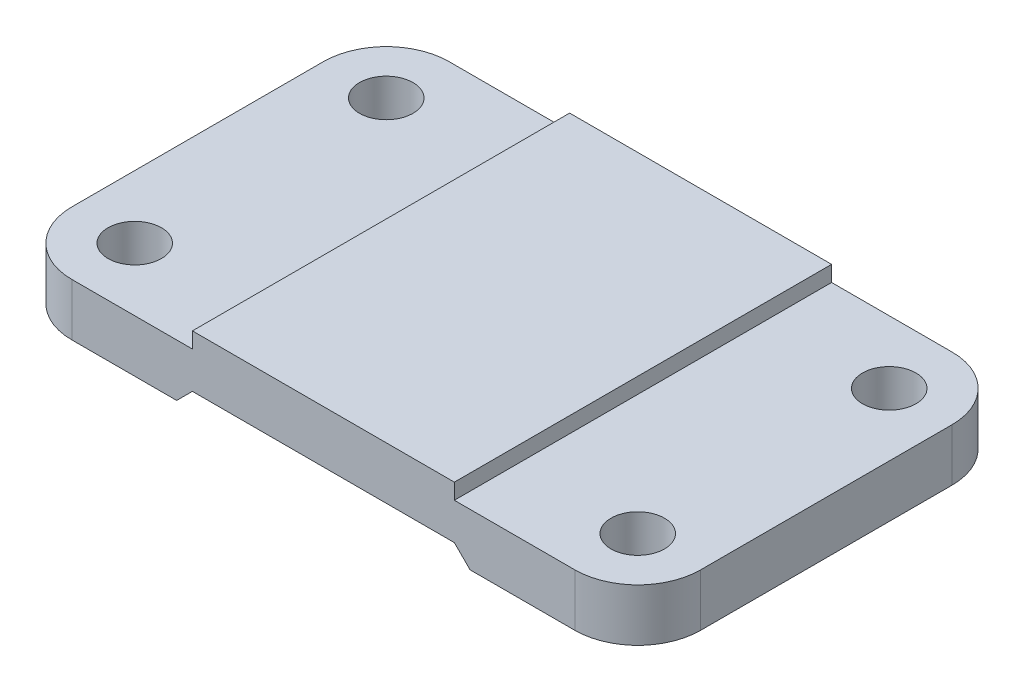
SolidWorks part; units mm, degrees
ref_plane "Front Plane" through (0, 0, 0) normal (0, 0, 1) x (1, 0, 0)
ref_plane "Top Plane" through (0, 0, 0) normal (0, 1, 0) x (1, 0, 0)
ref_plane "Right Plane" through (0, 0, 0) normal (1, 0, 0) x (0, 0, -1)
sketch "Sketch1" plane through (0, 0, 0) normal (0, 1, 0) x (1, 0, 0)
  line L1 (-60, -36) -> (60, -36)
  line L2 (-60, -36) -> (-60, 36)
  line L3 (-60, 36) -> (60, 36)
  line L4 (60, -36) -> (60, 36)
  line L5 (-60, -36) -> (60, 36) construction
  line L6 (-60, 36) -> (60, -36) construction
  point P0 (0, 0)
  dimension "D1" = 120
  dimension "D2" = 72
extrude "Boss-Extrude1" add sketch "Sketch1" along normal blind 10
fillet "Fillet1" radius 12 4 edges at (-60, 5, -36) (60, 5, -36) (60, 5, 36) (-60, 5, 36)
hole_wizard "M12 Tapped Hole1" positions "Sketch2" profile "Sketch3" tap size "M12" standard "DIN" end condition up to next
sketch "Sketch2" plane through (0, 0, 0) normal (0, 1, 0) x (1, 0, 0)
  point P6 (-48, 24)
  point P9 (48, 24)
  point P12 (48, -24)
  point P15 (-48, -24)
sketch "Sketch3" plane through (-48, 0, -24) normal (1, 0, 0) x (0, 0, -1)
  line L0 (0, 0) -> (0, 10)
  line L1 (0, 10) -> (5.1, 10)
  line L2 (5.1, 10) -> (5.1, 0.925)
  line L3 (5.1, 0.925) -> (6.025, 0)
  line L5 (6.025, 0) -> (0, 0)
  line L6 (-5.1, 0.925) -> (-6.025, 0) construction
  line L11 (0, -6.35) -> (0, 107.95) construction
  dimension "Thru Tap Drill Dia." = 10.2
  dimension "Thru Tap Drill Depth" = 10
  dimension "Near C'Sink Dia." = 12.05
  dimension "Near C'Sink Angle" = 90
cosmetic thread "Hole Thread1" parameters "D2"=12
cosmetic thread "Hole Thread2" parameters "D2"=12
cosmetic thread "Hole Thread3" parameters "D2"=12
cosmetic thread "Hole Thread4" parameters "D2"=12
sketch "Sketch4" plane through (0, 0, 0) normal (0, 1, 0) x (1, 0, 0)
  line L0 (48, 36) -> (-48, 36) construction
  line L1 (-25, -36) -> (25, -36)
  line L2 (-25, -36) -> (-25, 36)
  line L3 (-25, 36) -> (25, 36)
  line L4 (25, -36) -> (25, 36)
  line L5 (-25, -36) -> (25, 36) construction
  line L6 (-25, 36) -> (25, -36) construction
  point P0 (0, 0)
  dimension "D1" = 50
extrude "Boss-Extrude2" add sketch "Sketch4" along normal blind 3 from offset 10
sketch "Sketch5" plane through (0, 0, 0) normal (0, 0, 1) x (1, 0, 0)
  line L0 (-28, 0) -> (-25, 3)
  line L1 (-48, 0) -> (48, 0) construction
  line L2 (-25, 3) -> (25, 3)
  line L3 (25, 3) -> (28, 0)
  line L4 (28, 0) -> (-28, 0)
  line L5 (0, 0) -> (0, 13) construction
  line L6 (-25, 13) -> (25, 13) construction
  dimension "D1" = 56
  dimension "D2" = 3
extrude "Cut-Extrude1" cut sketch "Sketch5" against normal through all both and the other way through all
